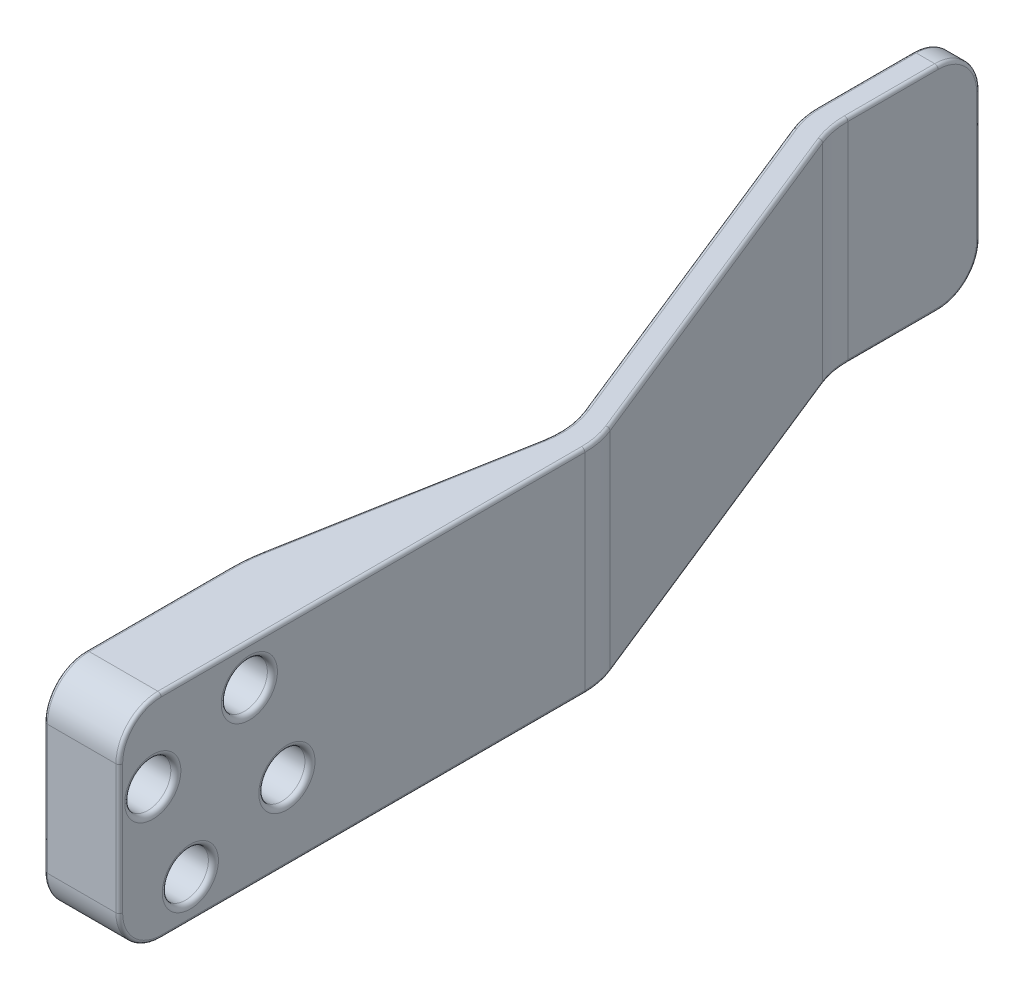
SolidWorks part; units mm, degrees
ref_plane "Front Plane" through (0, 0, 0) normal (0, 0, 1) x (1, 0, 0)
ref_plane "Top Plane" through (0, 0, 0) normal (0, 1, 0) x (1, 0, 0)
ref_plane "Right Plane" through (0, 0, 0) normal (1, 0, 0) x (0, 0, -1)
sketch "Sketch1" plane through (0, 0, 0) normal (0, 0, 1) x (1, 0, 0)
  line L0 (0, 0) -> (0, 24.7759) construction
  line L1 (0, 0) -> (34.3441, 0) construction
  line L3 (21, 12.7) -> (24, 12.7)
  line L4 (21, 12.7) -> (21, -12.7)
  line L5 (21, -12.7) -> (24, -12.7)
  line L6 (24, 12.7) -> (24, -12.7)
  line L7 (21, 12.7) -> (24, -12.7) construction
  line L8 (21, -12.7) -> (24, 12.7) construction
  point P3 (22.5, 0)
  dimension "D1" = 21
  dimension "D2" = 3
  dimension "D3" = 25.4
sketch "Sketch2" plane through (0, 0, 0) normal (0, 1, 0) x (1, 0, 0)
  line L0 (22.5, 0) -> (22.5, 57.2)
  line L1 (22.5, 57.2) -> (4, 103.2)
  line L2 (4, 103.2) -> (4, 121.2)
  line L3 (0, 0) -> (0, 51.9607) construction
  dimension "D1" = 4
  dimension "D2" = 18
  dimension "D3" = 121.2
  dimension "D4" = 64
sweep "Sweep1" add profiles "Sketch1" path "Sketch2"
sketch "Sketch3" plane through (24, 0, 0) normal (1, 0, 0) x (0, 0, -1)
  line L0 (12, 12.7) -> (12, -12.7) construction
  line L1 (57.4903, 12.7) -> (0, 12.7) construction
  line L2 (57.4903, -12.7) -> (0, -12.7) construction
  line L3 (0, 0) -> (57.4903, 0) construction
  line L4 (57.4903, -12.7) -> (57.4903, 12.7) construction
  line L6 (0, -12.7) -> (0, 12.7) construction
  circle A0 centre (4, 3.5196) radius 1.6
  circle A1 centre (12, 0) radius 8.74 construction
  circle A2 centre (15.5196, 8) radius 1.6
  circle A3 centre (20, -3.5196) radius 1.6
  circle A4 centre (8.4804, -8) radius 1.6
  point P26 (12, 0)
  dimension "D1" = 17.48
  dimension "D4" = 3.2
  dimension "D2" = 12
  dimension "D3" = 4
  dimension "D5" = 4
  dimension "D6" = 3.5196
  dimension "D7" = 8
extrude "Cut-Extrude1" cut sketch "Sketch3" against normal through all
sketch "Sketch4" plane through (21, 0, 0) normal (-1, 0, 0) x (0, 0, 1)
  line L0 (-56.9097, 12.7) -> (0, 12.7) construction
  line L1 (0, -12.7) -> (-24, -12.7)
  line L2 (0, -12.7) -> (0, 12.7)
  line L3 (0, 12.7) -> (-24, 12.7)
  line L4 (-24, -12.7) -> (-24, 12.7)
  circle A0 centre (-15.5196, 8) radius 1.6 construction
  circle A1 centre (-20, -3.5196) radius 1.6 construction
  circle A2 centre (-8.4804, -8) radius 1.6 construction
  circle A3 centre (-4, 3.5196) radius 1.6 construction
  circle A4 centre (-15.5196, 8) radius 1.6
  circle A5 centre (-20, -3.5196) radius 1.6
  circle A6 centre (-8.4804, -8) radius 1.6
  circle A7 centre (-4, 3.5196) radius 1.6
  dimension "D1" = 24
extrude "Boss-Extrude1" add sketch "Sketch4" along normal blind 5.98
sketch "Sketch6" plane through (0, 12.7, 0) normal (0, 1, 0) x (1, 0, 0)
  line L0 (15.02, 24) -> (21, 56.9097)
  line L2 (21, 56.9097) -> (21, 24) construction
  line L3 (21, 24) -> (15.02, 24)
  line L4 (21, 56.9097) -> (21, 24)
extrude "Boss-Extrude2" add sketch "Sketch6" against normal through all
fillet "Fillet1" radius 5 4 edges at (19.51, 12.7, 0) (19.51, -12.7, 0) (4, -12.7, -121.2) (4, 12.7, -121.2)
fillet "Fillet2" radius 10 4 edges at (5.5, 0, -103.4903) (2.5, 0, -102.9097) (24, 0, -57.4903) (21, 0, -56.9097)
fillet "Fillet3" radius 0.4 34 edges at (11.5725, -12.7, -80.3511) (2.6822, -12.7, -102.9449) (2.5, -12.7, -110.5226) (2.5, -11.2355, -119.7355) (2.5, 0, -121.2) (2.5, 11.2355, -119.7355) (2.5, 12.7, -110.5226) (2.6822, 12.7, -102.9449) (23.8178, 12.7, -57.4551) (24, 12.7, -30.2774) (24, 11.2355, -1.4645) (24, 0, 0) (24, -11.2355, -1.4645) (24, -12.7, -30.2774) (23.8178, -12.7, -57.4551) (14.75, -12.7, -80.4903) (5.6822, -12.7, -103.5256) (5.5, -12.7, -110.8129) (5.5, -11.2355, -119.7355) (5.5, 0, -121.2) (5.5, 11.2355, -119.7355) (5.5, 12.7, -110.8129) (5.6822, 12.7, -103.5256) (11.5725, 12.7, -80.3511) (14.75, 12.7, -80.4903) (15.02, -12.7, -14.5) (15.02, -11.2355, -1.4645) (15.02, 0, 0) (15.02, 11.2355, -1.4645) (15.02, 12.7, -14.5) (17.7519, 12.7, -39.0346) (20.5937, 12.7, -56.8684) (17.7519, -12.7, -39.0346) (20.5937, -12.7, -56.8684)
sketch "Sketch5" plane through (24, 0, 0) normal (1, 0, 0) x (0, 0, -1)
  circle A0 centre (4, 3.5196) radius 2.75
  circle A1 centre (15.5196, 8) radius 2.75
  circle A2 centre (20, -3.5196) radius 2.75
  circle A3 centre (8.4804, -8) radius 2.75
  dimension "D1" = 5.5
extrude "Cut-Extrude2" cut sketch "Sketch5" against normal offset from surface (6.98 mm away) 2 up to face at (15.02, -8, -6.8804)
fillet "Fillet7" radius 20 3 edges at (15.1372, -12.5828, -23.9894) (15.1372, 12.5828, -23.9894) (15.02, 0, -24)
fillet "Fillet8" radius 0.6 4 edges at (24, -0.7696, -20) (24, -5.25, -8.4804) (24, 6.2696, -4) (24, 10.75, -15.5196)
